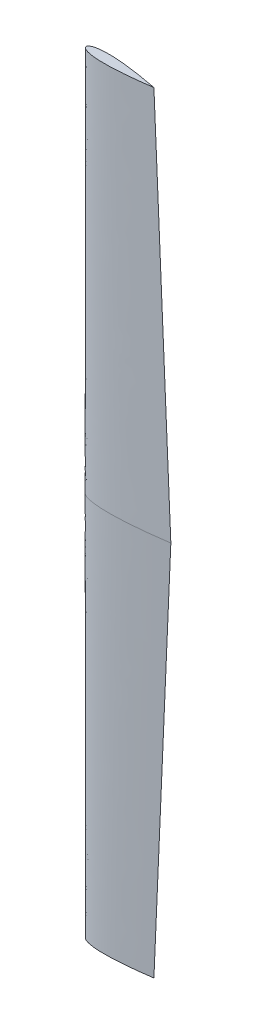
SolidWorks part; units mm, degrees
ref_plane "Front Plane" through (0, 0, 0) normal (0, 0, 1) x (1, 0, 0)
ref_plane "Top Plane" through (0, 0, 0) normal (0, 1, 0) x (1, 0, 0)
ref_plane "Right Plane" through (0, 0, 0) normal (1, 0, 0) x (0, 0, -1)
sketch "rootSketch" plane through (0, 0, 0) normal (0, 1, 0) x (1, 0, 0)
  line L0 (0, 0) -> (1500, 0) construction
  line L2 (128.9789, -42.2546) -> (130.939, 35.7208) construction
  line L3 (0, 0) -> (519.8358, -13.0676) construction
  spline S0 degree 4 poles (0, 0) (-0.0002, 0.5667) (0.0539, 1.484) (0.2615, 2.8006) (0.7775, 4.4995) (1.4672, 6.0739) (2.4738, 7.7799) (3.8987, 9.6474) (5.9417, 11.7552) (8.9487, 14.2083) (13.5292, 17.1361) (20.5336, 20.5651) (31.4063, 24.5153) (47.7297, 28.6693) (72.1656, 32.6344) (103.7641, 35.1569) (140.7266, 35.7505) (175.9809, 34.5913) (206.1498, 32.7093) (231.2548, 30.656) (251.3161, 28.7609) (271.3551, 26.6419) (291.372, 24.3247) (311.3671, 21.8288) (331.3419, 19.1703) (348.8007, 16.7128) (363.7545, 14.5178) (376.2044, 12.6323) (386.1643, 11.0892) (398.5968, 9.1212) (413.525, 6.6896) (430.8912, 3.7641) (450.7706, 0.2759) (468.0665, -2.8806) (482.9921, -5.7005) (495.2305, -8.0744) (504.1218, -9.8385) (511.0814, -11.24) (518.4727, -12.7541) (522.2266, -13.5316) (527.6229, -14.6589) (532.053, -15.5973) (537.2043, -16.6948) (542.7149, -17.8871) (549.3301, -19.3364) (555.7517, -20.7674) (561.4831, -22.0622) (565.9106, -23.077) (569.1697, -23.8299) (570.7836, -24.2051) (571.5942, -24.3939) (571.9999, -24.4886) knots 0 0 0 0 0 0.003846 0.006245 0.009023 0.012045 0.015501 0.01968 0.024954 0.031954 0.041824 0.056556 0.077861 0.110456 0.156157 0.224645 0.293132 0.36162 0.395864 0.430108 0.464352 0.498596 0.53284 0.567084 0.601327 0.635571 0.652693 0.669815 0.686937 0.704059 0.738303 0.772547 0.806791 0.841035 0.858157 0.875279 0.892401 0.900962 0.909523 0.920832 0.926487 0.932142 0.943452 0.954761 0.966071 0.977381 0.98869 0.994345 0.997173 1 1 1 1 1 construction
  spline S1 degree 4 poles (0, 0) (-0.0002, 0.5667) (0.0539, 1.484) (0.2615, 2.8006) (0.7775, 4.4995) (1.4672, 6.0739) (2.4738, 7.7799) (3.8987, 9.6474) (5.9417, 11.7552) (8.9487, 14.2083) (13.5292, 17.1361) (20.5336, 20.5651) (31.4063, 24.5153) (47.7297, 28.6693) (72.1656, 32.6344) (103.7641, 35.1569) (140.7266, 35.7505) (175.9809, 34.5913) (206.1498, 32.7093) (231.2548, 30.656) (251.3161, 28.7609) (271.3551, 26.6419) (291.372, 24.3247) (311.3671, 21.8288) (331.3419, 19.1703) (348.8007, 16.7128) (363.7545, 14.5178) (376.2044, 12.6323) (386.1643, 11.0892) (398.5968, 9.1212) (413.525, 6.6896) (430.8912, 3.7641) (450.7706, 0.2759) (468.0665, -2.8806) (482.9921, -5.7005) (495.2305, -8.0744) (504.1218, -9.8385) (511.0814, -11.24) (516.6376, -12.3782) (518.8783, -12.8398) (520, -13.0718) knots 0 0 0 0 0 0.003846 0.006245 0.009023 0.012045 0.015501 0.01968 0.024954 0.031954 0.041824 0.056556 0.077861 0.110456 0.156157 0.224645 0.293132 0.36162 0.395864 0.430108 0.464352 0.498596 0.53284 0.567084 0.601327 0.635571 0.652693 0.669815 0.686937 0.704059 0.738303 0.772547 0.806791 0.841035 0.858157 0.875279 0.892401 0.900962 0.909523 0.909523 0.909523 0.909523 0.909523
  spline S2 degree 4 poles (0, 0) (-0.0287, -0.566) (-0.0207, -1.4848) (0.1205, -2.8102) (0.5504, -4.5329) (1.1602, -6.14) (2.0798, -7.8944) (3.4091, -9.8311) (5.3435, -12.0388) (8.2235, -14.64) (12.6511, -17.7942) (19.4744, -21.5708) (30.1349, -26.0623) (46.229, -31.0313) (70.4348, -36.2191) (101.8666, -40.3261) (138.7526, -42.776) (174.0206, -43.3897) (204.246, -43.0258) (229.4225, -42.2365) (249.5536, -41.3518) (269.6737, -40.2423) (289.7818, -38.9338) (309.8771, -37.4457) (329.9602, -35.7941) (347.5204, -34.2169) (362.5656, -32.776) (375.0945, -31.5184) (385.1194, -30.4778) (397.635, -29.1369) (412.6666, -27.4585) (430.1578, -25.4092) (450.1874, -22.9243) (467.62, -20.6407) (482.6685, -18.5743) (495.0107, -16.8183) (503.9794, -15.5031) (511.0006, -14.4531) (518.4587, -13.3123) (522.2469, -12.7244) (527.693, -11.8697) (532.1647, -11.1551) (537.3646, -10.3177) (542.9282, -9.4038) (549.6079, -8.2887) (556.0932, -7.1822) (561.8824, -6.177) (566.3553, -5.386) (569.6481, -4.7977) (571.2788, -4.5041) (572.0979, -4.3562) (572.5079, -4.2821) knots 0 0 0 0 0 0.003846 0.006245 0.009023 0.012045 0.015501 0.01968 0.024954 0.031954 0.041824 0.056556 0.077861 0.110456 0.156157 0.224645 0.293132 0.36162 0.395864 0.430108 0.464352 0.498596 0.53284 0.567084 0.601327 0.635571 0.652693 0.669815 0.686937 0.704059 0.738303 0.772547 0.806791 0.841035 0.858157 0.875279 0.892401 0.900962 0.909523 0.920832 0.926487 0.932142 0.943452 0.954761 0.966071 0.977381 0.98869 0.994345 0.997173 1 1 1 1 1 construction
  spline S3 degree 4 poles (0, 0) (-0.0287, -0.566) (-0.0207, -1.4848) (0.1205, -2.8102) (0.5504, -4.5329) (1.1602, -6.14) (2.0798, -7.8944) (3.4091, -9.8311) (5.3435, -12.0388) (8.2235, -14.64) (12.6511, -17.7942) (19.4744, -21.5708) (30.1349, -26.0623) (46.229, -31.0313) (70.4348, -36.2191) (101.8666, -40.3261) (138.7526, -42.776) (174.0206, -43.3897) (204.246, -43.0258) (229.4225, -42.2365) (249.5536, -41.3518) (269.6737, -40.2423) (289.7818, -38.9338) (309.8771, -37.4457) (329.9602, -35.7941) (347.5204, -34.2169) (362.5656, -32.776) (375.0945, -31.5184) (385.1194, -30.4778) (397.635, -29.1369) (412.6666, -27.4585) (430.1578, -25.4092) (450.1874, -22.9243) (467.62, -20.6407) (482.6685, -18.5743) (495.0107, -16.8183) (503.9794, -15.5031) (511.0006, -14.4531) (516.607, -13.5955) (518.8681, -13.2471) (520, -13.0718) knots 0 0 0 0 0 0.003846 0.006245 0.009023 0.012045 0.015501 0.01968 0.024954 0.031954 0.041824 0.056556 0.077861 0.110456 0.156157 0.224645 0.293132 0.36162 0.395864 0.430108 0.464352 0.498596 0.53284 0.567084 0.601327 0.635571 0.652693 0.669815 0.686937 0.704059 0.738303 0.772547 0.806791 0.841035 0.858157 0.875279 0.892401 0.900962 0.909523 0.909523 0.909523 0.909523 0.909523
  point P1 (0, 0)
  point P4 (519.8358, 66.8203)
  point P10 (129.9589, -3.2669)
  dimension "incidenceAngle" = 1.44
  dimension "rootChord" = 520
  dimension "rootQuarterChord" = 130
  dimension "rootMaxThickness" = 78
ref_plane "Plane1" through (0, 2311.114, 0) normal (0, 1, 0) x (1, 0, 0)
sketch "tipSketch" plane through (0, 2311.114, 0) normal (0, 1, 0) x (1, 0, 0)
  line L0 (218.7894, 0) -> (520.1012, 0) construction
  line L3 (0, 0) -> (415.8686, -10.4541) construction
  line L4 (103.1831, -33.8037) -> (104.7512, 28.5766) construction
  spline S0 degree 4 poles (0, 0) (-0.0002, 0.4537) (0.0432, 1.1873) (0.2092, 2.2403) (0.622, 3.5997) (1.1738, 4.8591) (1.979, 6.224) (3.119, 7.7179) (4.7533, 9.4041) (7.1589, 11.3667) (10.8233, 13.7089) (16.4269, 16.4521) (25.1251, 19.6122) (38.1838, 22.9355) (57.7325, 26.1075) (83.0112, 28.1255) (112.5812, 28.6004) (140.7847, 27.6731) (164.9198, 26.1674) (185.0039, 24.5248) (201.0529, 23.0087) (217.0841, 21.3136) (233.0976, 19.4598) (249.0937, 17.463) (265.0735, 15.3362) (279.0406, 13.3702) (291.0035, 11.6142) (300.9637, 10.1058) (308.9311, 8.8715) (318.8781, 7.2968) (330.8189, 5.3519) (344.7148, 3.0109) (360.6136, 0.2213) (374.4576, -2.3054) (386.387, -4.559) (396.1959, -6.4619) (403.2749, -7.8662) (408.898, -8.9988) (414.744, -10.1962) (418.3515, -10.9434) (424.1991, -12.1675) (428.7951, -13.1496) (434.3702, -14.3507) (439.3394, -15.4433) (444.6879, -16.6318) (449.7679, -17.7825) (453.7438, -18.6936) (456.289, -19.2854) (457.6027, -19.5914) knots 0 0 0 0 0 0.003846 0.006245 0.009023 0.012045 0.015501 0.01968 0.024954 0.031954 0.041824 0.056556 0.077861 0.110456 0.156157 0.224645 0.293132 0.36162 0.395864 0.430108 0.464352 0.498596 0.53284 0.567084 0.601327 0.635571 0.652693 0.669815 0.686937 0.704059 0.738303 0.772547 0.806791 0.841035 0.858157 0.875279 0.892401 0.900962 0.909523 0.920832 0.932142 0.943452 0.954761 0.966071 0.977381 0.98869 1 1 1 1 1 construction
  spline S1 degree 4 poles (0, 0) (-0.0002, 0.4537) (0.0432, 1.1873) (0.2092, 2.2403) (0.622, 3.5997) (1.1738, 4.8591) (1.979, 6.224) (3.119, 7.7179) (4.7533, 9.4041) (7.1589, 11.3667) (10.8233, 13.7089) (16.4269, 16.4521) (25.1251, 19.6122) (38.1838, 22.9355) (57.7325, 26.1075) (83.0112, 28.1255) (112.5812, 28.6004) (140.7847, 27.6731) (164.9198, 26.1674) (185.0039, 24.5248) (201.0529, 23.0087) (217.0841, 21.3136) (233.0976, 19.4598) (249.0937, 17.463) (265.0735, 15.3362) (279.0406, 13.3702) (291.0035, 11.6142) (300.9637, 10.1058) (308.9311, 8.8715) (318.8781, 7.2968) (330.8189, 5.3519) (344.7148, 3.0109) (360.6136, 0.2213) (374.4576, -2.3054) (386.387, -4.559) (396.1959, -6.4619) (403.2749, -7.8662) (408.898, -8.9988) (413.2926, -9.8989) (415.1026, -10.2718) (416, -10.4574) knots 0 0 0 0 0 0.003846 0.006245 0.009023 0.012045 0.015501 0.01968 0.024954 0.031954 0.041824 0.056556 0.077861 0.110456 0.156157 0.224645 0.293132 0.36162 0.395864 0.430108 0.464352 0.498596 0.53284 0.567084 0.601327 0.635571 0.652693 0.669815 0.686937 0.704059 0.738303 0.772547 0.806791 0.841035 0.858157 0.875279 0.892401 0.900962 0.909523 0.909523 0.909523 0.909523 0.909523
  spline S2 degree 4 poles (0, 0) (-0.023, -0.4531) (-0.0166, -1.1879) (0.0964, -2.248) (0.4403, -3.6264) (0.9282, -4.9119) (1.6638, -6.3155) (2.7273, -7.8649) (4.2748, -9.6311) (6.5788, -11.712) (10.1209, -14.2354) (15.5795, -17.2566) (24.1079, -20.8498) (36.9832, -24.825) (56.3478, -28.9753) (81.4933, -32.2609) (111.002, -34.2208) (139.2165, -34.7118) (163.3968, -34.4206) (183.538, -33.7892) (199.6429, -33.0814) (215.739, -32.1939) (231.8255, -31.147) (247.9017, -29.9565) (263.9681, -28.6353) (278.0164, -27.3735) (290.0524, -26.2208) (300.0758, -25.2147) (308.0952, -24.3823) (318.1087, -23.3094) (330.1321, -21.967) (344.1281, -20.3271) (360.147, -18.3399) (374.1004, -16.5119) (386.128, -14.8605) (396.0201, -13.4529) (403.1608, -12.406) (408.8337, -11.5574) (414.7324, -10.6552) (418.373, -10.0902) (424.2747, -9.1615) (428.9142, -8.4115) (434.5426, -7.4921) (439.5604, -6.6505) (444.9619, -5.7323) (450.0933, -4.8382) (454.1099, -4.1281) (456.6816, -3.6649) (458.0091, -3.4253) knots 0 0 0 0 0 0.003846 0.006245 0.009023 0.012045 0.015501 0.01968 0.024954 0.031954 0.041824 0.056556 0.077861 0.110456 0.156157 0.224645 0.293132 0.36162 0.395864 0.430108 0.464352 0.498596 0.53284 0.567084 0.601327 0.635571 0.652693 0.669815 0.686937 0.704059 0.738303 0.772547 0.806791 0.841035 0.858157 0.875279 0.892401 0.900962 0.909523 0.920832 0.932142 0.943452 0.954761 0.966071 0.977381 0.98869 1 1 1 1 1 construction
  spline S3 degree 4 poles (0, 0) (-0.023, -0.4531) (-0.0166, -1.1879) (0.0964, -2.248) (0.4403, -3.6264) (0.9282, -4.9119) (1.6638, -6.3155) (2.7273, -7.8649) (4.2748, -9.6311) (6.5788, -11.712) (10.1209, -14.2354) (15.5795, -17.2566) (24.1079, -20.8498) (36.9832, -24.825) (56.3478, -28.9753) (81.4933, -32.2609) (111.002, -34.2208) (139.2165, -34.7118) (163.3968, -34.4206) (183.538, -33.7892) (199.6429, -33.0814) (215.739, -32.1939) (231.8255, -31.147) (247.9017, -29.9565) (263.9681, -28.6353) (278.0164, -27.3735) (290.0524, -26.2208) (300.0758, -25.2147) (308.0952, -24.3823) (318.1087, -23.3094) (330.1321, -21.967) (344.1281, -20.3271) (360.147, -18.3399) (374.1004, -16.5119) (386.128, -14.8605) (396.0201, -13.4529) (403.1608, -12.406) (408.8337, -11.5574) (413.2679, -10.8792) (415.0944, -10.5977) (416, -10.4574) knots 0 0 0 0 0 0.003846 0.006245 0.009023 0.012045 0.015501 0.01968 0.024954 0.031954 0.041824 0.056556 0.077861 0.110456 0.156157 0.224645 0.293132 0.36162 0.395864 0.430108 0.464352 0.498596 0.53284 0.567084 0.601327 0.635571 0.652693 0.669815 0.686937 0.704059 0.738303 0.772547 0.806791 0.841035 0.858157 0.875279 0.892401 0.900962 0.909523 0.909523 0.909523 0.909523 0.909523
  point P1 (0, 0)
  point P2 (0, 0)
  point P10 (103.9672, -2.6135)
  dimension "incidenceAngle" = 1.44
  dimension "tipChord" = 416
  dimension "tipQuarterChord" = 104
  dimension "tipMaxThickness" = 62.4
  dimension "sweepOffset" = 0
  dimension "D1" = 0
loft "Loft1" add profiles "rootSketch", "tipSketch" connector at (0, 0, 0) connector at (0, 2311.114, 0)
mirror "Mirror1" about plane through (0, 0, 0) normal (0, 1, 0) of "Loft1"
ref_plane "Plane2" through (520, 0, 0) normal (1, 0, 0) x (0, 0, -1)
sketch "elevatorSketch" plane through (0, 0, 0) normal (0, 0, 1) x (1, 0, 0)
  line L0 (316.6205, 0.1248) -> (269.9487, 1728.7133)
  line L1 (0, 1733.3355) -> (265.2, 1733.3355) construction
  line L2 (0, 0) -> (312, 0) construction
  line L3 (-0.0163, 0) -> (520, 0) construction
  line L4 (312, 0) -> (265.2, 1733.3355)
  line L5 (269.9487, 1728.7133) -> (785.2, 1728.7133)
  line L7 (265.2, 1733.3355) -> (785.2, 1733.3355)
  line L8 (312, 0) -> (316.6205, 0.1248)
  line L9 (785.2, 1733.3355) -> (785.2, 1728.7133)
  dimension "elevatorEndyLoc" = 1733.3355
  dimension "elevatorEndxLoc" = 265.2
  dimension "D1" = 312
  dimension "D2" = 520
  dimension "D3" = 4.6222
extrude "Cut-Extrude2" [suppressed] cut sketch "elevatorSketch" against normal blind 200 and the other way blind 200 contours L0 L5 L9 L7 L4 L8
mirror "Mirror2" [suppressed] about plane through (0, 0, 0) normal (0, 1, 0)
equation "\"rootChord\"= 0.52"
equation "\"NACAairfoil\"= 0015"
equation "\"incidentAngle\"= 1.44"
equation "\"aspectRatio\"= 8.8889"
equation "\"taperRatio\"= 0.8"
equation "\"sweepAngle\"= 0'H-stab sweep angle"
equation "\"rootChord@rootSketch\"=(\"rootChord\"+\"rootChord\")/2"
equation "\"rootQuarterChord@rootSketch\" = \"rootChord@rootSketch\" / 4"
equation "\"rootMaxThickness@rootSketch\" = \"rootChord\" * \"NACAairfoil\" / 100"
equation "\"halfSpan@Plane1\"=\"halfSpan\""
equation "\"tipQuarterChord@tipSketch\"=\"tipChord@tipSketch\"/4"
equation "\"tipMaxThickness@tipSketch\"=\"tipChord@tipSketch\"*\"NACAairfoil\"/100"
equation "\"rootChord@Plane2\"=\"rootChord@rootSketch\""
equation "\"elevatorWidth\"= 0.75'Elevator width as a percentage of H-stab span"
equation "\"elevatorEndyLoc@elevatorSketch\"=\"elevatorWidth\"*\"halfSpan@Plane1\""
equation "\"elevatorEndxLoc@elevatorSketch\"=\"elevatorEndyLoc@elevatorSketch\" * tan ( \"sweepAngle\" )  + 0.6 *  ( \"rootChord@rootSketch\" + \"elevatorEndyLoc@elevatorSketch\" *  (  (  ( \"tipChord@tipSketch\" - \"rootChord@rootSketch\" )  / \"halfSpan@Plane1\" )  )  )"
equation "\"D1@elevatorSketch\"=0.6*\"rootChord@rootSketch\""
equation "\"D2@elevatorSketch\"=1*\"rootChord@rootSketch\""
equation "\"D3@elevatorSketch\" = \"halfSpan\" / 500"
equation "\"halfSpan\"= \"rootChord\" * \"aspectRatio\" / 2'H-stab half Span"
equation "\"sweepOffset@tipSketch\" = \"halfSpan\" * tan ( \"sweepAngle\" ) "
equation "\"incidenceAngle@rootSketch\"=\"incidentAngle\""
